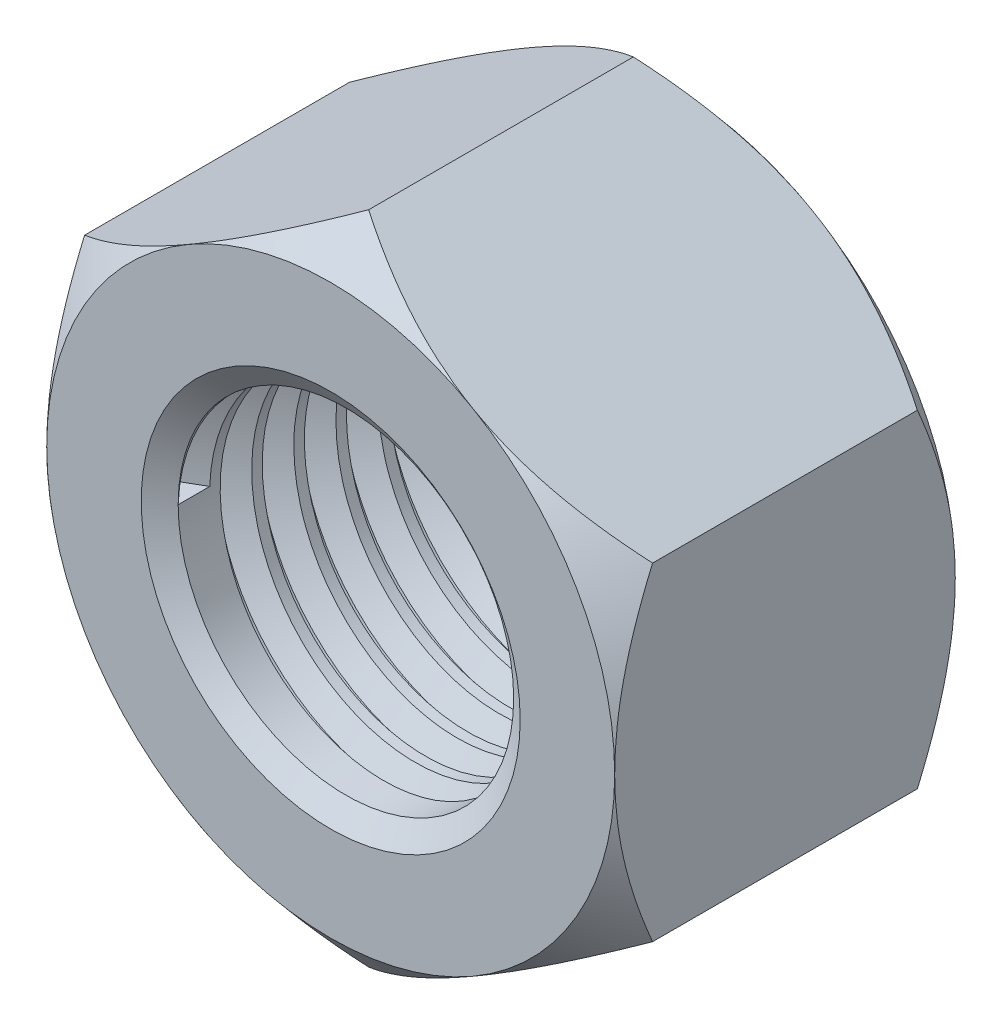
SolidWorks part; units mm, degrees
extrude "BaseNut" add sketch "BaseNutSke" against normal blind 8.5598
sketch "BaseNutSke" plane through (0, 0, 0) normal (0, 0, 1) x (1, 0, 0)
  line L6 (7.1374, 4.1208) -> (7.1374, -4.1208)
  line L7 (-7.1374, 4.1208) -> (-7.1374, -4.1208)
  line L8 (7.1374, 4.1208) -> (0, 8.2416)
  line L9 (0, 8.2416) -> (-7.1374, 4.1208)
  line L10 (-7.1374, -4.1208) -> (0, -8.2416)
  line L11 (0, -8.2416) -> (7.1374, -4.1208)
  circle A0 centre (0, 0) radius 4.2164
  dimension "D2" = 7.1374
  dimension "D3" = 7.1374
  dimension "D1" = 120
  dimension "D4" = 7.1374
cosmetic thread "ThreadCosmetic" [suppressed] parameters "Thread_major"=9.525
pattern_linear "ThdSchPat" [suppressed]
revolve "ThreadSchematic" [suppressed] cut sketch "ThdSchSke" angle 360 about L6
sketch "ThdSchSke" plane through (0, 0, 0) normal (0, 1, 0) x (1, 0, 0)
  line L0 (-4.7625, 0.0254) -> (-4.2164, 0.4078)
  line L1 (-4.2164, 0.4078) -> (-2.1082, 0.4078)
  line L2 (-2.1082, 0.4078) -> (-2.1082, -0.357)
  line L3 (-2.1082, -0.357) -> (-4.2164, -0.357)
  line L4 (-4.2164, -0.357) -> (-4.7625, 0.0254)
  line L5 (-3.175, 1.0592) -> (3.175, 1.0592) construction
  line L6 (0, 1.0592) -> (0, -2.9874) construction
  line L7 (0, 8.152) -> (0, 0.3824) construction
  dimension "SideAngle" = 55
  dimension "Advance" = 1.0592
  dimension "D1" = 0.0254
ref_plane "Plane1" through (0, 0, 0) normal (0, 0, 1) x (1, 0, 0)
ref_plane "Plane2" through (0, 0, 0) normal (0, 1, 0) x (1, 0, 0)
ref_plane "Plane3" through (0, 0, 0) normal (1, 0, 0) x (0, 0, -1)
sketch "Sketch4" plane through (0, 0, 0) normal (1, 0, 0) x (0, 0, -1)
  line L0 (8.5598, 7.1374) -> (8.1534, 7.1374)
  line L1 (8.5598, 7.1374) -> (8.5598, 20.9416)
  line L2 (8.1534, 20.9416) -> (8.5598, 20.9416)
  line L3 (8.1534, 20.9416) -> (8.1534, 7.1374)
  line L4 (0, 0) -> (34.925, 0) construction
  line L6 (8.5598, 4.1208) -> (8.5598, 8.2416) construction
  line L7 (0, 7.1374) -> (-12.7, 7.1374)
  line L8 (0, 4.1208) -> (0, 8.2416) construction
  line L9 (0.9525, 8.2416) -> (0.9525, 20.9416)
  line L10 (0.9525, 20.9416) -> (-12.7, 20.9416)
  line L11 (-12.7, 20.9416) -> (-12.7, 7.1374)
  line L12 (0, 7.1374) -> (0.9525, 8.2416)
  line L14 (0, 4.1208) -> (0, -4.1208) construction
  line L15 (8.5598, 8.2416) -> (0, 8.2416) construction
  dimension "D1" = 7.1374
  dimension "D2" = 0.9525
  dimension "D3" = 12.7
  dimension "D4" = 12.7
revolve "Bearing-Face" [suppressed] cut sketch "Sketch4" angle 360 about L4
sketch "Sketch3" plane through (0, 0, 0) normal (1, 0, 0) x (0, 0, -1)
  line L0 (8.5598, 7.1374) -> (7.6073, 8.2416)
  line L1 (7.6073, 8.2416) -> (7.6073, 20.9416)
  line L2 (7.6073, 20.9416) -> (21.2598, 20.9416)
  line L3 (21.2598, 20.9416) -> (21.2598, 7.1374)
  line L4 (21.2598, 7.1374) -> (8.5598, 7.1374)
  line L5 (8.5598, 4.1208) -> (8.5598, 8.2416) construction
  line L6 (8.5598, 8.2416) -> (0, 8.2416) construction
  line L7 (0, 0) -> (38.6776, 0) construction
  line L8 (8.5598, 0) -> (0, 0) construction
  line L9 (4.2799, 8.2416) -> (4.2799, 44.222) construction
  line L10 (0.9525, 20.9416) -> (-12.7, 20.9416)
  line L11 (-12.7, 20.9416) -> (-12.7, 7.1374)
  line L12 (-12.7, 7.1374) -> (0, 7.1374)
  line L13 (0, 7.1374) -> (0.9525, 8.2416)
  line L14 (0.9525, 8.2416) -> (0.9525, 20.9416)
  line L16 (8.5598, 8.2416) -> (0, 8.2416) construction
  dimension "D1" = 7.1374
  dimension "D2" = 0.9525
  dimension "D4" = 12.7
  dimension "D3" = 12.7
revolve "Double-Chamfer" cut sketch "Sketch3" angle 360 about L7
sketch "Sketch5" plane through (0, 0, 0) normal (1, 0, 0) x (0, 0, -1)
  line L0 (8.5344, 4.7625) -> (8.1138, 4.1618)
  line L1 (8.5852, 4.7625) -> (8.5344, 4.7625)
  line L2 (8.5852, 4.7625) -> (8.5852, 4.1618)
  line L3 (8.5852, 4.1618) -> (8.1138, 4.1618)
  line L6 (-0.0508, 4.7625) -> (0, 4.7625)
  line L7 (0, 4.7625) -> (0.4206, 4.1618)
  line L9 (0.4206, 4.1618) -> (-0.0508, 4.1618)
  line L10 (-0.0508, 4.1618) -> (-0.0508, 4.7625)
  line L11 (25.0375, 0) -> (38.388, 0) construction
  line L12 (8.5598, 0) -> (0, 0) construction
  dimension "D1" = 35
  dimension "D2" = 0.0508
  dimension "ThreadMajor" = 4.7625
  dimension "Offset1" = 8.5852
revolve "EndChamfer" cut sketch "Sketch5" angle 360 about L11
thread "Thread1" pitch 1.0583 method cut profile "Thread Profile1" start angle 0, offset 0, length 0, pitch 1.0583, diameter 8.4328
ref_plane "Plane4" through (-4.2164, 0, -0.3824) normal (0, -1, 0) x (-1, 0, 0)
sketch "Thread Profile1" plane through (-4.2164, 0, -0.3824) normal (0, -1, 0) x (-1, 0, 0)
  line L0 (0, 0) -> (0, 1.0583) construction
  line L1 (0, 0) -> (0.5728, 0.3307)
  line L2 (0.5728, 0.3307) -> (0.5728, 0.463)
  line L3 (0.5728, 0.463) -> (0, 0.7937)
  line L4 (0.5728, 0.3969) -> (0, 0.3969) construction
  line L11 (0, 0) -> (0, 0.7937)
  point P2 (0, 0)
  dimension "Pitch" = 1.0583
  dimension "Profile_Angle" = 60
  dimension "Profile_Land" = 0.1323
  dimension "Profile_Height" = 0.5728
equation "\"D2@BaseNutSke\" = \"Width_flats@BaseNutSke\" / 2"
equation "\"D3@BaseNutSke\" = \"Width_flats@BaseNutSke\" / 2"
equation "\"D1@Sketch3\" = \"Width_flats@BaseNutSke\" /2"
equation "\"D2@Sketch3\" = \"Thread_major@ThreadCosmetic\" *.1"
equation "\"D1@Sketch4\" = \"D2@BaseNutSke\""
equation "\"D2@Sketch4\" = \"Thread_major@ThreadCosmetic\" *.10"
equation "\"D4@BaseNutSke\" = \"D3@BaseNutSke\""
equation "\"Thread_major@ThdSchSke\" = \"Thread_major@ThreadCosmetic\""
equation "\"Tap_Drill@ThdSchSke\" = \"Tap_drill@BaseNutSke\""
equation "\"OverCut@ThdSchSke\" = \"Tap_Drill@ThdSchSke\" * 0.5"
equation "\"Num_threads@ThdSchPat\" = int(  ( \"Thickness@BaseNut\" - 0.002 ) / \"Advance@ThdSchSke\" + 0.999 )  + 1"
equation "\"Advance@ThdSchPat\" = ( \"Thickness@BaseNut\" - 0.002 ) /  (\"Num_threads@ThdSchPat\" - 1) 'relax it"
equation "' \"Num_threads@ThdSchPat\" = \"Num_threads@ThdSchPat\" - sgn( \"Num_threads@ThdSchPat\" - 1) '---chamfered tips only---"
equation "\"ThreadMajor@Sketch5\" = \"Thread_major@ThreadCosmetic\" * 0.5"
equation "\"ChamferDepth@Sketch5\" = (\"Thread_major@ThreadCosmetic\" - \"Tap_drill@BaseNutSke\") * 0.55"
equation "\"Offset1@Sketch5\" = \"Thickness@BaseNut\" + 0.001"
equation "\"Offset2@Sketch5\" = \"Offset1@Sketch5\" + 0.002"
